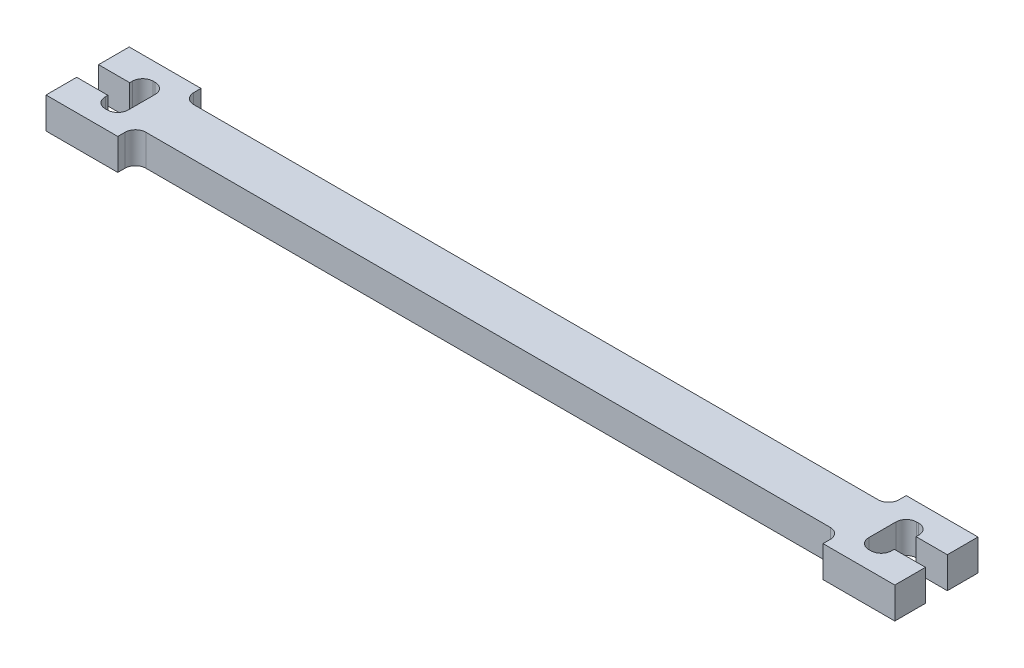
SolidWorks part; units mm, degrees
ref_plane "Front Plane" through (0, 0, 0) normal (0, 0, 1) x (1, 0, 0)
ref_plane "Top Plane" through (0, 0, 0) normal (0, 1, 0) x (1, 0, 0)
ref_plane "Right Plane" through (0, 0, 0) normal (1, 0, 0) x (0, 0, -1)
sketch "Sketch1" plane through (0, 0, 0) normal (0, 1, 0) x (1, 0, 0)
  line L0 (-40.8, 0) -> (40.8, 0) construction
  line L1 (-40.8, 4) -> (40.8, 4)
  line L2 (-40.8, 4) -> (-40.8, -4)
  line L3 (-40.8, -4) -> (40.8, -4)
  line L4 (40.8, 4) -> (40.8, -4)
  line L5 (-40.8, 4) -> (40.8, -4) construction
  line L6 (-40.8, -4) -> (40.8, 4) construction
  line L7 (-35.6, 2.3) -> (-35.6, 4) construction
  line L8 (-40.8, 1.05) -> (-37.8, 1.05)
  line L9 (-40.8, 1.05) -> (-40.8, -1.05)
  line L10 (-40.8, -1.05) -> (-37.8, -1.05)
  line L11 (-37.8, 1.05) -> (-37.8, -1.05)
  line L12 (-40.8, 1.05) -> (-37.8, -1.05) construction
  line L13 (-40.8, -1.05) -> (-37.8, 1.05) construction
  line L14 (-37.8, 2.3) -> (-35.6, 2.3)
  line L15 (-37.8, 2.3) -> (-37.8, -2.3)
  line L16 (-37.8, -2.3) -> (-35.6, -2.3)
  line L17 (-35.6, 2.3) -> (-35.6, -2.3)
  line L18 (-37.8, 2.3) -> (-35.6, -2.3) construction
  line L19 (-37.8, -2.3) -> (-35.6, 2.3) construction
  line L20 (-33.9, 2.3) -> (33.9, 2.3)
  line L21 (-33.9, 2.3) -> (-33.9, -2.3)
  line L22 (-33.9, -2.3) -> (33.9, -2.3)
  line L23 (33.9, 2.3) -> (33.9, -2.3)
  line L24 (-33.9, 2.3) -> (33.9, -2.3) construction
  line L25 (-33.9, -2.3) -> (33.9, 2.3) construction
  line L26 (-35.6, 2.3) -> (-33.9, 2.3) construction
  line L27 (-33.9, 2.3) -> (-33.9, 4)
  line L28 (-33.9, -2.3) -> (-33.9, -4)
  line L29 (0, 4) -> (0, -4) construction
  line L30 (33.9, -2.3) -> (33.9, -4)
  line L31 (-40.8, 4) -> (-40.8, -4)
  line L32 (40.8, 4) -> (40.8, -4)
  line L33 (33.9, 2.3) -> (33.9, 4)
  line L34 (40.8, -1.05) -> (37.8, -1.05)
  line L35 (37.8, -2.3) -> (35.6, -2.3)
  line L36 (35.6, 2.3) -> (35.6, -2.3)
  line L37 (37.8, 2.3) -> (35.6, 2.3)
  line L38 (37.8, 2.3) -> (37.8, -2.3)
  line L39 (40.8, 1.05) -> (37.8, 1.05)
  point P0 (0, 0)
  point P8 (-39.3, 0)
  point P13 (-36.7, 0)
  point P18 (0, 0)
  dimension "D1" = 8
  dimension "D2" = 81.6
  dimension "D3" = 3
  dimension "D4" = 2.2
  dimension "D5" = 4.6
  dimension "D6" = 2.1
extrude "Base shape" add sketch "Sketch1" along normal blind 3 contours L23 L20 L21 L22 | L28 L21 L27 L1 L2 L8 L15 L14 L17 L16 L10 L3 | L39 L4 L1 L33 L23 L30 L3 L32 L34 L38 L35 L36 L37 region at (-37.35, 0, -3.8944) region at (37.35, 0, -3.8944) region at (0, 0, 0)
fillet "Milling fillets" radius 1 12 edges at (37.8, 1.5, 2.3) (-35.6, 1.5, 2.3) (-37.8, 1.5, 2.3) (35.6, 1.5, 2.3) (35.6, 1.5, -2.3) (-37.8, 1.5, -2.3) (-35.6, 1.5, -2.3) (37.8, 1.5, -2.3) (33.9, 1.5, 2.3) (33.9, 1.5, -2.3) (-33.9, 1.5, -2.3) (-33.9, 1.5, 2.3)
sketch "Center axis sketch" plane through (40.8, 0, 0) normal (1, 0, 0) x (0, 0, -1)
  line L0 (-1.05, 0) -> (1.05, 3) construction
  point P4 (0, 1.5)
ref_axis "Center axis" through (-46.4653, 1.5, 0) along (1, 0, 0)
